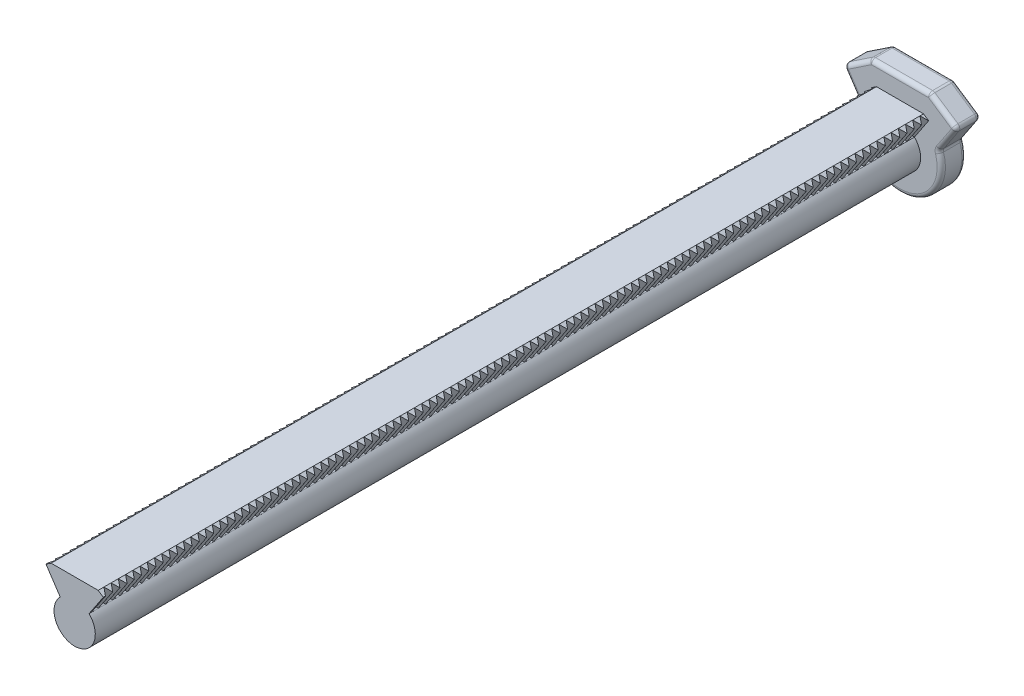
SolidWorks part; units mm, degrees
ref_plane "Alzado" through (0, 0, 0) normal (0, 0, 1) x (1, 0, 0)
ref_plane "Planta" through (0, 0, 0) normal (0, 1, 0) x (1, 0, 0)
ref_plane "Vista lateral" through (0, 0, 0) normal (1, 0, 0) x (0, 0, -1)
sketch "Croquis1" plane through (0, 0, 0) normal (0, 0, 1) x (1, 0, 0)
  line L0 (-3.4937, 3.5769) -> (3.4937, 3.5769)
  line L1 (3.4937, 3.5769) -> (7.5, 9.5769)
  line L2 (7.5, 9.5769) -> (-7.5, 9.5769)
  line L3 (-7.5, 9.5769) -> (-3.4937, 3.5769)
  circle A0 centre (0, 0) radius 5
  dimension "D1" = 10
  dimension "D2" = 15
  dimension "D3" = 6
extrude "Saliente-Extruir1" add sketch "Croquis1" along normal blind 200 contours L0 A0 | L0 A0 | A0 L1 L2 L3
ref_plane "Plano3" through (0, 0, 0) normal (1, 0, 0) x (0, 0, -1)
chamfer "Chaflán2" distance 1 angle 90 2 edges at (-7.5, 9.5769, 100) (7.5, 9.5769, 100)
sketch "Croquis2" plane through (6.1802, 9.2557, 0) normal (0.5553, 0.8316, 0) x (0.8316, -0.5553, 0)
  line L5 (0.9193, 0) -> (0.9193, -1.7293)
  line L6 (0.9193, 0) -> (0.9193, -200) construction
  line L7 (0.9193, -1.7293) -> (-0.5783, -0.8647)
  line L8 (-0.5783, -200) -> (-0.5783, 0) construction
  line L9 (-0.5783, -0.8647) -> (0.9193, 0)
extrude "Cortar-Extruir1" cut sketch "Croquis2" against normal blind 6.2
pattern_linear "MatrizL1" count 114 spacing 1.75 along (0, 0, 1) of "Cortar-Extruir1"
mirror "Simetría1" about plane through (0, 0, 0) normal (1, 0, 0) of "MatrizL1", "Cortar-Extruir1"
sketch "Croquis3" plane through (0, 0, 0) normal (0, 0, -1) x (-1, 0, 0)
  line L14 (9.3985, 3.416) -> (13.8795, 10.1269)
  line L15 (13.8795, 10.1269) -> (7.215, 14.5769)
  line L16 (7.215, 14.5769) -> (-7.215, 14.5769)
  line L17 (-7.215, 14.5769) -> (-13.8795, 10.1269)
  line L18 (-13.8795, 10.1269) -> (-9.3985, 3.416)
  line L19 (9.3985, 3.416) -> (13.8795, 10.1269)
  line L20 (13.8795, 10.1269) -> (7.215, 14.5769)
  line L21 (7.215, 14.5769) -> (-7.215, 14.5769)
  line L22 (-7.215, 14.5769) -> (-13.8795, 10.1269)
  line L23 (-13.8795, 10.1269) -> (-9.3985, 3.416)
  arc A2 (-9.3985, 3.416) -> (9.3985, 3.416) centre (0, 0) ccw
  arc A3 (-9.3985, 3.416) -> (9.3985, 3.416) centre (0, 0) ccw
  dimension "D1" = 5
extrude "Saliente-Extruir2" add sketch "Croquis3" along normal blind 6
fillet "Redondeo1" radius 1 18 edges at (0, -10, 0) (-9.3985, 3.416, -3) (-11.639, 6.7715, 0) (9.3985, 3.416, -3) (11.639, 6.7715, 0) (13.8795, 10.1269, -3) (10.5472, 12.3519, 0) (-13.8795, 10.1269, -3) (-10.5472, 12.3519, 0) (-7.215, 14.5769, -3) (7.215, 14.5769, -3) (0, 14.5769, 0) (11.639, 6.7715, -6) (10.5472, 12.3519, -6) (0, 14.5769, -6) (-10.5472, 12.3519, -6) (-11.639, 6.7715, -6) (0, -10, -6)
